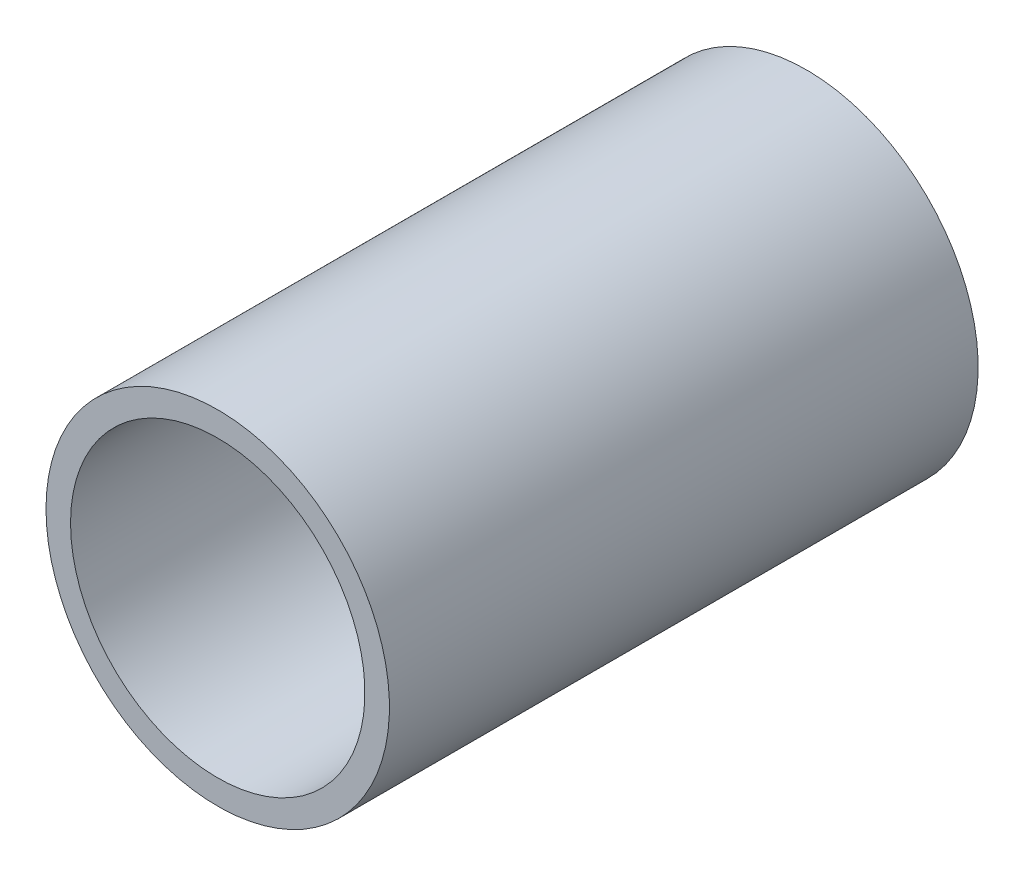
SolidWorks part; units mm, degrees
material "Acrylic (Medium-high impact)"
ref_plane "Front Plane" through (0, 0, 0) normal (0, 0, 1) x (1, 0, 0)
ref_plane "Top Plane" through (0, 0, 0) normal (0, 1, 0) x (1, 0, 0)
ref_plane "Right Plane" through (0, 0, 0) normal (1, 0, 0) x (0, 0, -1)
sketch "Sketch1" plane through (0, 0, 0) normal (0, 0, 1) x (1, 0, 0)
  circle A0 centre (0, 0) radius 19.05
  circle A1 centre (0, 0) radius 22.225
  dimension "D1" = 38.1
  dimension "D2" = 44.45
extrude "Boss-Extrude1" add sketch "Sketch1" along normal blind 76.2
